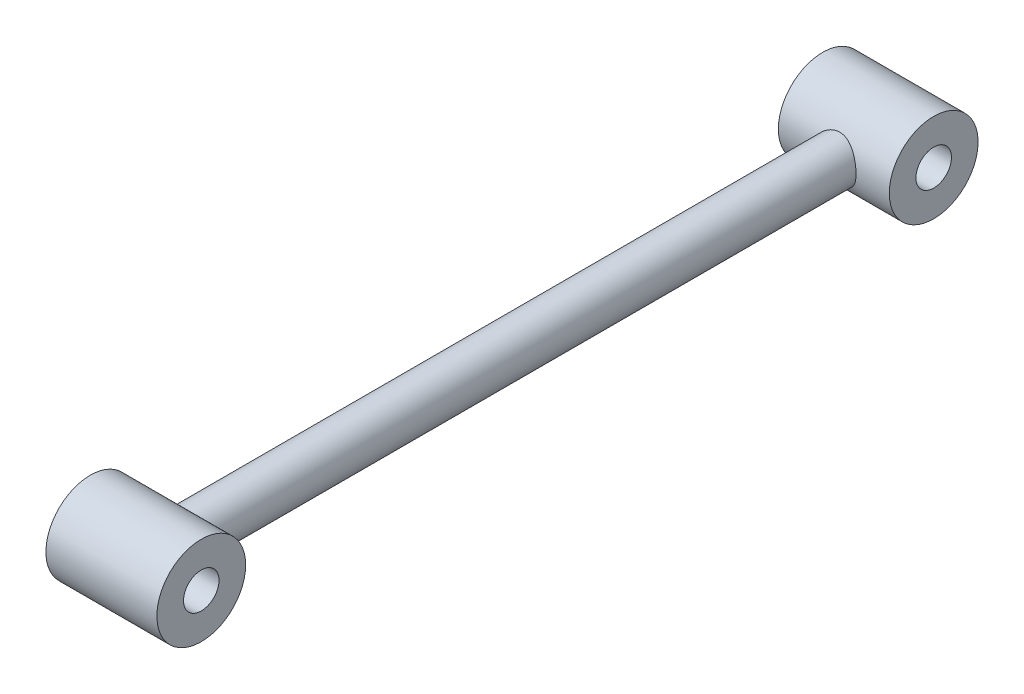
SolidWorks part; units mm, degrees
ref_plane "Front Plane" through (0, 0, 0) normal (0, 0, 1) x (1, 0, 0)
ref_plane "Top Plane" through (0, 0, 0) normal (0, 1, 0) x (1, 0, 0)
ref_plane "Right Plane" through (0, 0, 0) normal (1, 0, 0) x (0, 0, -1)
sketch "Sketch1" plane through (0, 0, 0) normal (0, 0, 1) x (1, 0, 0)
  circle A0 centre (0, 0) radius 5
  dimension "D1" = 10
extrude "Boss-Extrude1" add sketch "Sketch1" along normal blind 165
sketch "Sketch2" plane through (0, 0, 0) normal (1, 0, 0) x (0, 0, -1)
  line L0 (-165, 5) -> (-165, -5) construction
  line L1 (-82.5, -5) -> (-82.5, 20.6362) construction
  line L2 (-165, -5) -> (0, -5) construction
  circle A0 centre (-165, 0) radius 4
  circle A1 centre (-165, 0) radius 10
  circle A2 centre (0, 0) radius 10
  circle A3 centre (0, 0) radius 4
  point P12 (0, 0)
  point P13 (0, 0)
  point P14 (0, 0)
  point P15 (0, 0)
  dimension "D1" = 8
  dimension "D2" = 20
extrude "Boss-Extrude2" add sketch "Sketch2" along normal blind 12.5 and the other way blind 12.5
extrude "Cut-Extrude1" cut sketch "Sketch2<2>" against normal through all both and the other way through all contours A0 | A3 region at (0, 0, 165) region at (0, 0, 0)
sketch "Sketch2<2>" plane through (0, 0, 0) normal (1, 0, 0) x (0, 0, -1) same geometry as "Sketch2"
